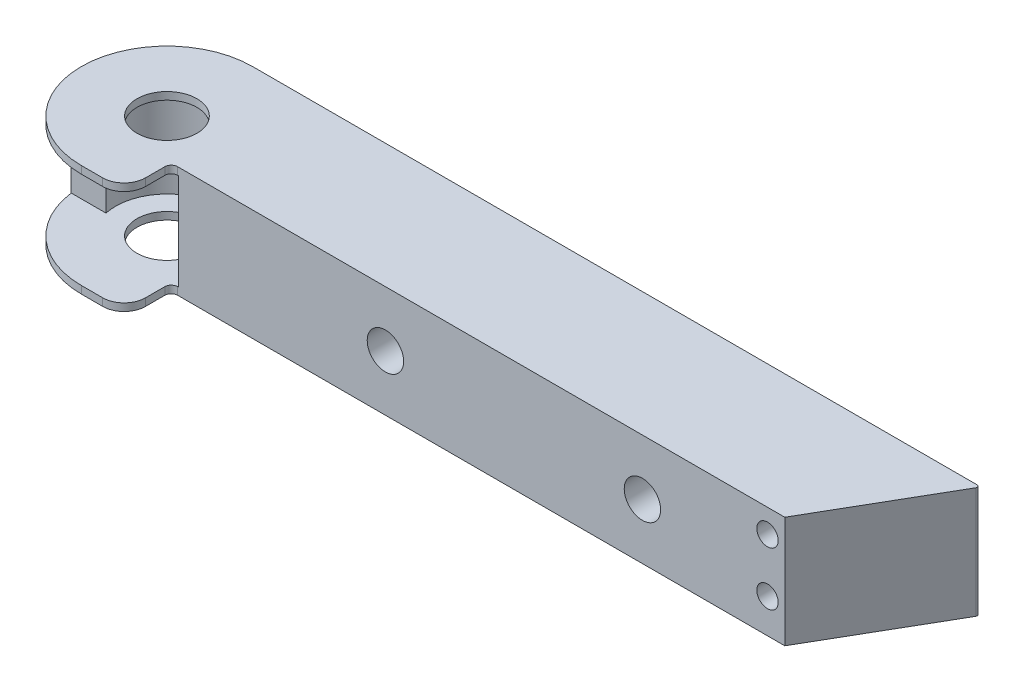
SolidWorks part; units mm, degrees
material "Nylon 6/10"
ref_plane "Front Plane" through (0, 0, 0) normal (0, 0, 1) x (1, 0, 0)
ref_plane "Top Plane" through (0, 0, 0) normal (0, 1, 0) x (1, 0, 0)
ref_plane "Right Plane" through (0, 0, 0) normal (1, 0, 0) x (0, 0, -1)
sketch "Sketch1" plane through (0, 0, 0) normal (0, 1, 0) x (1, 0, 0)
  line L0 (0, 0) -> (38, 0)
  line L1 (38, 0) -> (30, -8)
  line L2 (30, -8) -> (0, -8)
  line L3 (0, -8) -> (0, 0)
  dimension "D1" = 38
  dimension "D2" = 30
  dimension "D3" = 8
extrude "Boss-Extrude1" add sketch "Sketch1" along normal blind 5.5
sketch "Sketch3" plane through (0, 5.5, 0) normal (0, 1, 0) x (1, 0, 0)
  line L0 (2, 0) -> (2, -2) construction
  line L1 (38, 0) -> (0, 0) construction
  line L2 (2, -2) -> (0, -2) construction
  line L3 (0, 0) -> (0, -8) construction
  dimension "D1" = 2
  dimension "D2" = 2
sketch "Sketch4" plane through (0, 0, 8) normal (0, 0, 1) x (1, 0, 0)
  line L12 (0, 0.5) -> (6, 0.5)
  line L13 (0, 5.5) -> (0, 0) construction
  line L14 (6, 0.5) -> (6, 0)
  line L15 (0, 0) -> (30, 0) construction
  line L16 (6, 0) -> (38, 0)
  line L17 (38, 0) -> (38, 5.5)
  line L18 (38, 5.5) -> (6, 5.5)
  line L19 (0, 5.5) -> (30, 5.5) construction
  line L20 (6, 5.5) -> (6, 5)
  line L21 (6, 5) -> (0, 5)
  line L22 (0, 5) -> (0, 0.5)
  dimension "D1" = 6
  dimension "D2" = 6
  dimension "D3" = 0.5
  dimension "D4" = 0.5
extrude "Cut-Extrude1" cut sketch "Sketch4" against normal blind 3.5
fillet "Fillet2" radius 4 3 edges at (0, 0.25, 8) (0, 5.25, 8) (0, 2.75, 0)
sketch "Sketch13" plane through (0, 0, 0) normal (0, 0, -1) x (-1, 0, 0)
  line L0 (-38, 0) -> (-4, 0) construction
  line L3 (-4, 0) -> (-4, 5.5) construction
  circle A0 centre (-33.84, 4.25) radius 0.5
  circle A1 centre (-33.84, 1.75) radius 0.5
  dimension "D1" = 1
  dimension "D2" = 1
  dimension "D4" = 1.75
  dimension "D5" = 29.84
  dimension "D3" = 2.5
sketch "Sketch15" plane through (0, 0, 0) normal (0, 0, -1) x (-1, 0, 0)
  line L0 (-4, 2.75) -> (-28, 2.75) construction
  line L1 (-4, 0) -> (-4, 5.5) construction
  line L2 (-28, 2.75) -> (-28, 5.5) construction
  line L3 (-38, 5.5) -> (-4, 5.5) construction
  line L4 (-23, 2.75) -> (-23, 5.5) construction
  dimension "D1" = 5
  dimension "D2" = 19
sketch "Sketch19" plane through (0, 5.5, 0) normal (0, 1, 0) x (1, 0, 0)
  circle A0 centre (4, -4) radius 1.4
  point P0 (4, -4)
extrude "Cut-Extrude3" cut sketch "Sketch19" against normal blind 6.3
sketch "Sketch21" plane through (0, 0.5, 0) normal (0, 1, 0) x (1, 0, 0)
  circle A0 centre (4, -4) radius 2.4
  point P0 (4, -4)
extrude "Cut-Extrude4" cut sketch "Sketch21" along normal blind 4.5
sketch "Sketch22" plane through (0, 0, 4.5) normal (0, 0, 1) x (1, 0, 0)
  line L0 (6.3473, 5) -> (6, 5)
  line L1 (6, 5) -> (6, 5.5)
  line L2 (6, 5.5) -> (33.5, 5.5)
  line L3 (33.5, 5.5) -> (33.5, 0)
  line L4 (33.5, 0) -> (6, 0)
  line L5 (6, 0) -> (6, 0.5)
  line L6 (6, 0.5) -> (6.3473, 0.5)
  line L7 (6.3473, 0.5) -> (6.3473, 5)
extrude "Boss-Extrude3" add sketch "Sketch22" along normal blind 1.3
fillet "Fillet5" radius 0.3 2 edges at (6, 0.25, 5.8) (6, 5.25, 5.8)
fillet "Fillet6" radius 1 2 edges at (6, 0.25, 8) (6, 5.25, 8)
sketch "Sketch25" plane through (0, 5.5, 0) normal (0, 1, 0) x (1, 0, 0)
  line L0 (38, 0) -> (33.5, -4.5)
  line L1 (33.5, -4.5) -> (33.5, -5.8)
  line L2 (33.5, -5.8) -> (34.6462, -5.8)
  line L3 (34.6462, -5.8) -> (38, 0)
  line L4 (38, 0) -> (4, 0) construction
  dimension "D1" = 59.962
extrude "Boss-Extrude4" add sketch "Sketch25" against normal blind 5.5
extrude "Cut-Extrude5" cut sketch "Sketch13" against normal blind 6.5
fillet "Fillet7" radius 0.1 1 edges at (38, 2.75, 0)
ref_plane "Plane1" through (0, 5.5, 0) normal (0, 1, 0) x (1, 0, 0)
sketch "Sketch30" plane through (0, 5.5, 0) normal (0, 1, 0) x (1, 0, 0)
  line L0 (39.9507, 0.4511) -> (-1.7146, 0.4511)
  line L1 (-1.7146, 0.4511) -> (-1.7146, -8.528)
  line L2 (-1.7146, -8.528) -> (39.9507, -8.528)
  line L3 (39.9507, -8.528) -> (39.9507, 0.4511)
extrude "Cut-Extrude6" cut sketch "Sketch30" against normal blind 0.15
ref_plane "Plane2" through (0, 0, 0) normal (0, -1, 0) x (-1, 0, 0)
sketch "Sketch31" plane through (0, 0, 0) normal (0, -1, 0) x (-1, 0, 0)
  line L0 (1.8378, 0.4313) -> (1.8378, -8.4743)
  line L1 (1.8378, -8.4743) -> (-39.7571, -8.4743)
  line L2 (-39.7571, -8.4743) -> (-39.7571, 0.4313)
  line L3 (-39.7571, 0.4313) -> (1.8378, 0.4313)
extrude "Cut-Extrude7" cut sketch "Sketch31" against normal blind 0.15
sketch "Sketch32" plane through (0, 0, 0) normal (0, 0, -1) x (-1, 0, 0)
  line L0 (-4, 0.15) -> (-4, 5.35) construction
  point P0 (-16, 2.75)
  point P3 (-4, 2.75)
  point P4 (-28, 2.75)
  dimension "D1" = 12
  dimension "D2" = 24
hole_wizard "M1.6 Clearance Hole1" positions "Sketch35" profile "Sketch36" hole size "M1.6" standard "ANSI Metric" end condition through all
sketch "Sketch35" plane through (0, 0, 0) normal (0, 0, -1) x (-1, 0, 0)
  point P0 (-16, 2.75)
  point P3 (-28, 2.75)
sketch "Sketch36" plane through (16, 2.75, 0) normal (1, 0, 0) x (0, 1, 0)
  line L0 (0, 0) -> (0, 8)
  line L1 (0, 8) -> (0.85, 8)
  line L2 (0.85, 8) -> (0.85, 0)
  line L5 (0.85, 0) -> (0, 0)
  line L11 (0, -6.35) -> (0, 107.95) construction
  dimension "Thru Hole Dia." = 1.7
  dimension "Thru Hole Depth" = 8
